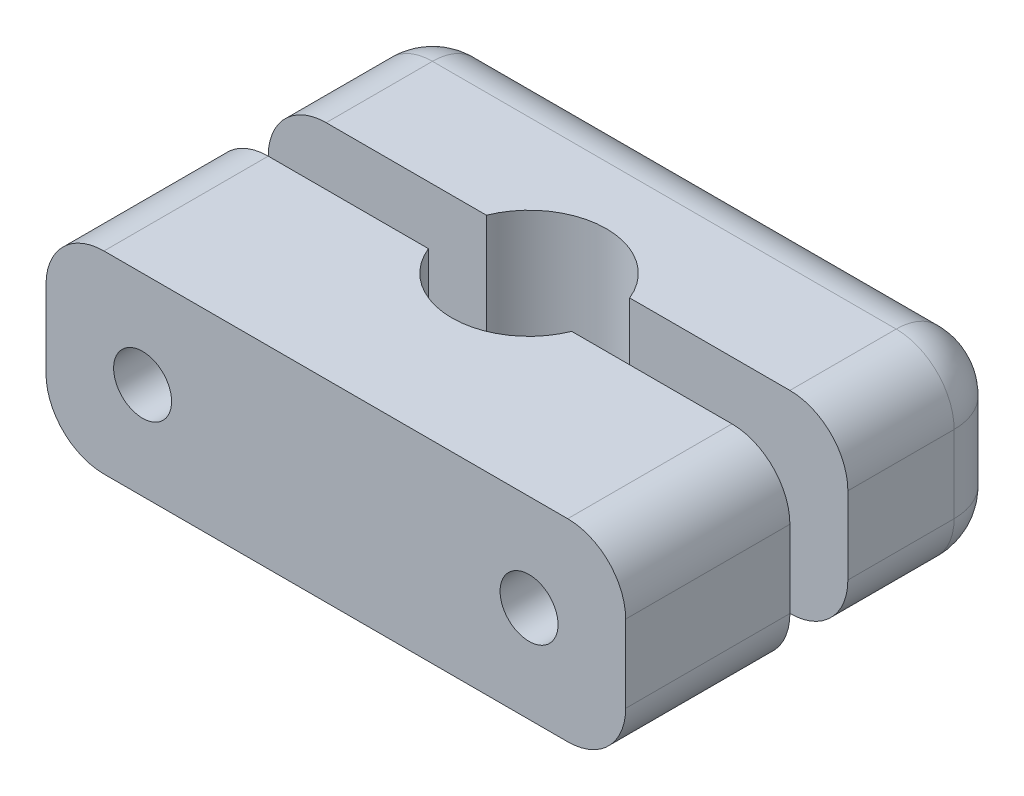
SolidWorks part; units mm, degrees
material "ABS"
ref_plane "Front Plane" through (0, 0, 0) normal (0, 0, 1) x (1, 0, 0)
ref_plane "Top Plane" through (0, 0, 0) normal (0, 1, 0) x (1, 0, 0)
ref_plane "Right Plane" through (0, 0, 0) normal (1, 0, 0) x (0, 0, -1)
sketch "Sketch1" plane through (0, 0, 0) normal (0, 1, 0) x (1, 0, 0)
  line L1 (-15, -10) -> (15, -10)
  line L2 (-15, -10) -> (-15, 10)
  line L3 (-15, 10) -> (15, 10)
  line L4 (15, -10) -> (15, 10)
  line L5 (-15, -10) -> (15, 10) construction
  line L6 (-15, 10) -> (15, -10) construction
  point P0 (0, 0)
  dimension "D1" = 30
  dimension "D2" = 20
extrude "Boss-Extrude1" add sketch "Sketch1" along normal blind 10
sketch "Sketch2" plane through (0, 10, 0) normal (0, 1, 0) x (1, 0, 0)
  circle A0 centre (0, 0) radius 4
  dimension "D1" = 8
extrude "Cut-Extrude1" cut sketch "Sketch2" against normal blind 10
sketch "Sketch3" plane through (0, 0, 10) normal (0, 0, 1) x (1, 0, 0)
  line L0 (-15, 0) -> (15, 0) construction
  line L1 (-15, 10) -> (-15, 0) construction
  circle A0 centre (-10, 5) radius 1.5
  circle A1 centre (10, 5) radius 1.5
  dimension "D1" = 3
  dimension "D5" = 3
  dimension "D2" = 5
  dimension "D3" = 5
  dimension "D4" = 20
extrude "Cut-Extrude2" cut sketch "Sketch3" against normal through all
sketch "Sketch4" plane through (0, 0, -10) normal (0, 0, -1) x (-1, 0, 0)
  circle A0 centre (-10, 5) radius 2.5
  circle A1 centre (10, 5) radius 2.5
  dimension "D1" = 5
  dimension "D2" = 5
extrude "Cut-Extrude3" cut sketch "Sketch4" against normal blind 6
sketch "Sketch5" plane through (0, 10, 0) normal (0, 1, 0) x (1, 0, 0)
  line L0 (-15, 10) -> (-15, -10) construction
  line L1 (15, 1.5) -> (-15, 1.5)
  line L2 (15, 1.5) -> (15, -1.5)
  line L3 (15, -1.5) -> (-15, -1.5)
  line L4 (-15, 1.5) -> (-15, -1.5)
  line L5 (15, 1.5) -> (-15, -1.5) construction
  line L6 (15, -1.5) -> (-15, 1.5) construction
  point P0 (0, 0)
  dimension "D1" = 3
extrude "Cut-Extrude4" cut sketch "Sketch5" against normal through all
fillet "Fillet2" radius 3 8 edges at (15, 0, -5.75) (15, 10, -5.75) (-15, 0, -5.75) (-15, 10, -5.75) (0, 10, -10) (0, 0, -10) (15, 5, -10) (-15, 5, -10)
fillet "Fillet3" radius 3 4 edges at (15, 10, 5.75) (15, 0, 5.75) (-15, 0, 5.75) (-15, 10, 5.75)
